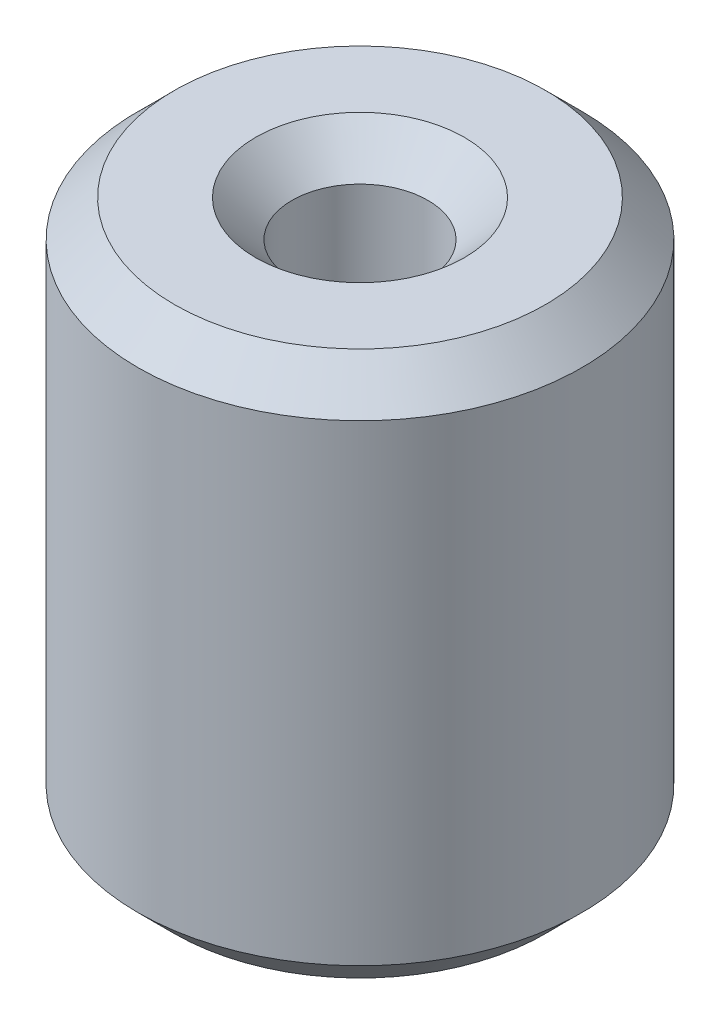
SolidWorks part; units mm, degrees
ref_plane "Front Plane" through (0, 0, 0) normal (0, 0, 1) x (1, 0, 0)
ref_plane "Top Plane" through (0, 0, 0) normal (0, 1, 0) x (1, 0, 0)
ref_plane "Right Plane" through (0, 0, 0) normal (1, 0, 0) x (0, 0, -1)
sketch "Sketch1" plane through (0, 0, 0) normal (0, 1, 0) x (1, 0, 0)
  circle A0 centre (0, 0) radius 7.5
  dimension "SLEEVE_OD" = 15
extrude "Boss-Extrude1" add sketch "Sketch1" along normal blind 18.4088
sketch "Sketch2" plane through (0, 0, 0) normal (0, 1, 0) x (1, 0, 0)
  circle A0 centre (0, 0) radius 2.2962
  dimension "BORE_D" = 4.5924
extrude "Cut-Extrude1" cut sketch "Sketch2" along normal through all
chamfer "Chamfer1" distance 1.2301 angle 45 4 edges at (0, 18.4088, 2.2962) (0, 0, 2.2962) (0, 0, 7.5) (0, 18.4088, 7.5)
